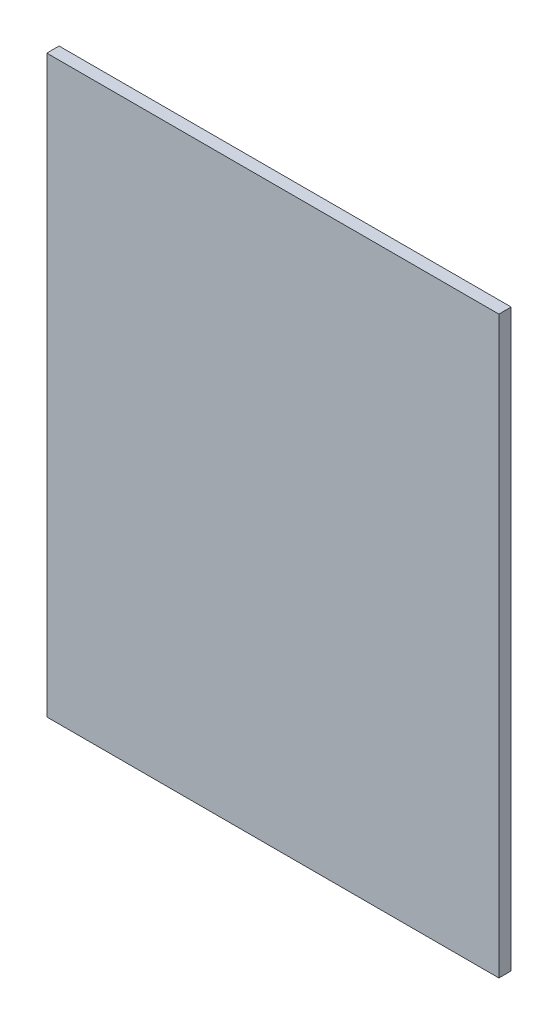
SolidWorks part; units mm, degrees
ref_plane "Alzado" through (0, 0, 0) normal (0, 0, 1) x (1, 0, 0)
ref_plane "Planta" through (0, 0, 0) normal (0, 1, 0) x (1, 0, 0)
ref_plane "Vista lateral" through (0, 0, 0) normal (1, 0, 0) x (0, 0, -1)
sketch "Croquis1" plane through (0, 0, 0) normal (0, 0, 1) x (1, 0, 0)
  line L1 (-18.4, -23.4) -> (18.4, -23.4)
  line L2 (-18.4, -23.4) -> (-18.4, 23.4)
  line L3 (-18.4, 23.4) -> (18.4, 23.4)
  line L4 (18.4, -23.4) -> (18.4, 23.4)
  line L5 (-18.4, -23.4) -> (18.4, 23.4) construction
  line L6 (-18.4, 23.4) -> (18.4, -23.4) construction
  point P0 (0, 0)
  dimension "D1" = 46.8
  dimension "D2" = 36.8
extrude "Saliente-Extruir1" add sketch "Croquis1" along normal blind 1
